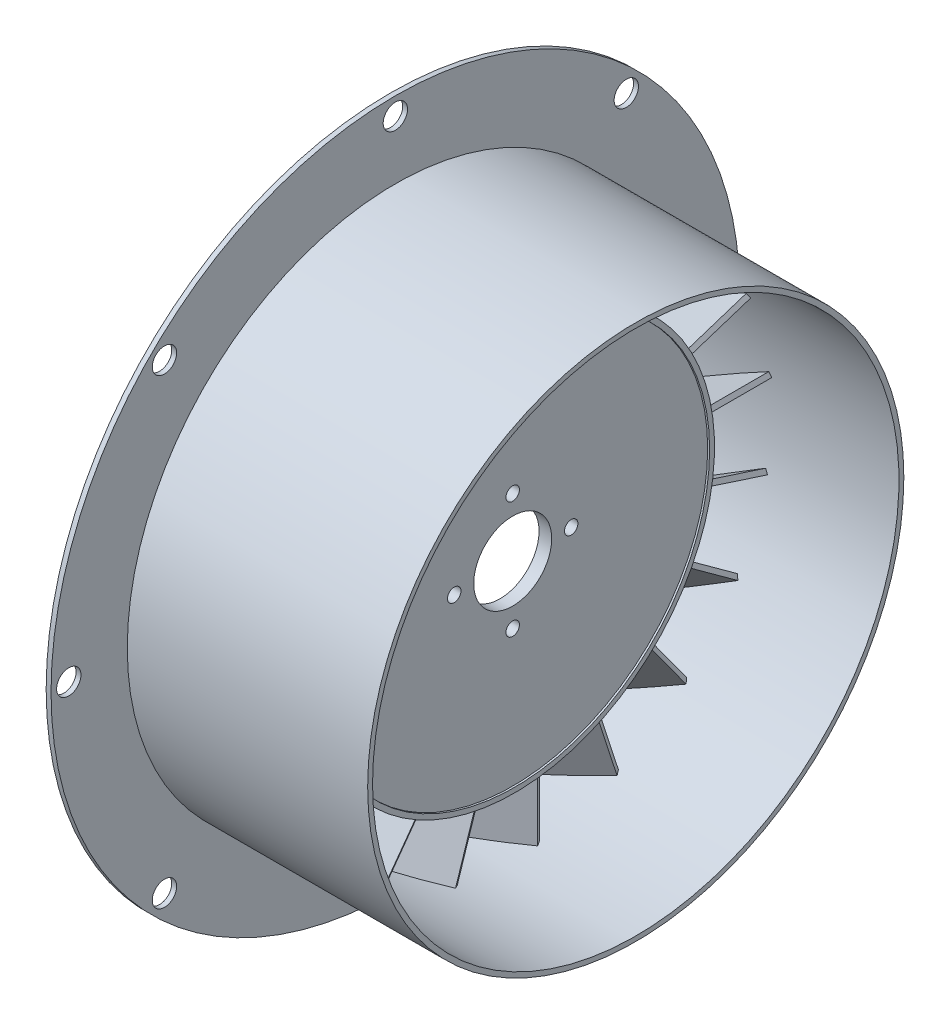
SolidWorks part; units mm, degrees
ref_plane "Front Plane" through (0, 0, 0) normal (0, 0, 1) x (1, 0, 0)
ref_plane "Top Plane" through (0, 0, 0) normal (0, 1, 0) x (1, 0, 0)
ref_plane "Right Plane" through (0, 0, 0) normal (1, 0, 0) x (0, 0, -1)
sketch "Sketch1" plane through (0, 0, 0) normal (0, 1, 0) x (1, 0, 0)
  line L0 (3.302, 0) -> (3.302, 50.8)
  line L1 (3.302, 50.8) -> (3.81, 50.8)
  line L2 (3.81, 50.8) -> (3.81, 52.07)
  line L3 (3.81, 52.07) -> (-25.4, 52.07)
  line L4 (-25.4, 52.07) -> (-25.4, 50.8)
  line L5 (-25.4, 50.8) -> (0, 50.8)
  line L6 (0, 50.8) -> (0, 0)
  line L7 (0, 0) -> (3.302, 0)
  dimension "D1" = 3.302
  dimension "D2" = 1.27
  dimension "D3" = 50.8
  dimension "D4" = 29.21
  dimension "D5" = 25.4
revolve "Revolve1" add sketch "Sketch1" angle 360 about L7
ref_plane "Plane1" through (0, 0, 83.82) normal (0, 0, 1) x (1, 0, 0)
sketch "Sketch2" plane through (0, 0, 83.82) normal (0, 0, 1) x (1, 0, 0)
  line L0 (-24.3107, 7.0701) -> (2.0857, -8.1699)
  line L1 (2.0857, -8.1699) -> (2.7207, -7.0701)
  line L3 (2.7207, -7.0701) -> (-23.6757, 8.1699)
  line L4 (-23.6757, 8.1699) -> (-24.3107, 7.0701)
  line L5 (-25.4, 0) -> (3.81, 0) construction
  line L6 (-25.4, 52.07) -> (-25.4, -52.07) construction
  line L7 (3.81, -52.07) -> (3.81, 52.07) construction
  line L8 (-11.1125, -0.5499) -> (-10.4775, 0.5499) construction
  point P4 (-10.795, 0)
  point P13 (-10.795, 0)
  dimension "D1" = 1.27
  dimension "D2" = 30
  dimension "D3" = 30.48
extrude "Boss-Extrude1" add sketch "Sketch2" along normal blind 16.51 from surface starting at face at (-25.4, 0, 52.07)
pattern_circular "CirPattern15" count 20 over 360 about axis through (3.81, 0, 0) along (-1, 0, 0) of "Boss-Extrude1"
sketch "Sketch7" plane through (3.302, 0, 0) normal (1, 0, 0) x (0, 0, -1)
  circle A0 centre (0, 15.24) radius 1.7526
  circle A1 centre (0, 0) radius 10.16
  circle A2 centre (15.24, 0) radius 1.7526
  circle A3 centre (0, -15.24) radius 1.7526
  circle A4 centre (-15.24, 0) radius 1.7526
  point P14 (0, 0)
  dimension "D1" = 3.5052
  dimension "D3" = 20.32
  dimension "D2" = 15.24
  dimension "D4" = 4
extrude "Cut-Extrude1" cut sketch "Sketch7" against normal through all
sketch "Sketch8" plane through (0, 0, 0) normal (0, 0, 1) x (1, 0, 0)
  line L0 (35.3606, 69.85) -> (35.3606, 68.58)
  line L1 (35.3606, 68.58) -> (-28.5393, 68.58)
  line L2 (-28.5393, -76.2) -> (-28.5393, 76.2) construction
  line L3 (-28.5393, 68.58) -> (-28.5393, 89.7168)
  line L5 (-28.5393, 89.7168) -> (-27.2693, 89.7168)
  line L6 (-27.2693, 89.7168) -> (-27.2693, 69.85)
  line L7 (-27.2693, 69.85) -> (35.3606, 69.85)
  line L8 (35.3606, -69.85) -> (35.3606, 69.85) construction
  line L9 (-93.6879, 0) -> (-7.1026, 0) construction
  line L10 (0, 0) -> (79.505, 0) construction
  dimension "D1" = 68.58
  dimension "D2" = 1.27
  dimension "D3" = 1.27
revolve "Revolve2" add sketch "Sketch8" angle 360 about L10
sketch "Sketch9" plane through (-27.2693, 0, 0) normal (1, 0, 0) x (0, 0, -1)
  circle A0 centre (0, 85.09) radius 3.175
  circle A1 centre (60.1677, 60.1677) radius 3.175
  circle A2 centre (85.09, 0) radius 3.175
  circle A3 centre (60.1677, -60.1677) radius 3.175
  circle A4 centre (0, -85.09) radius 3.175
  circle A5 centre (-60.1677, -60.1677) radius 3.175
  circle A6 centre (-85.09, 0) radius 3.175
  circle A7 centre (-60.1677, 60.1677) radius 3.175
  point P19 (0, 0)
  dimension "D1" = 6.35
  dimension "D2" = 85.09
  dimension "D3" = 8
extrude "Cut-Extrude2" cut sketch "Sketch9" against normal blind 2.54
